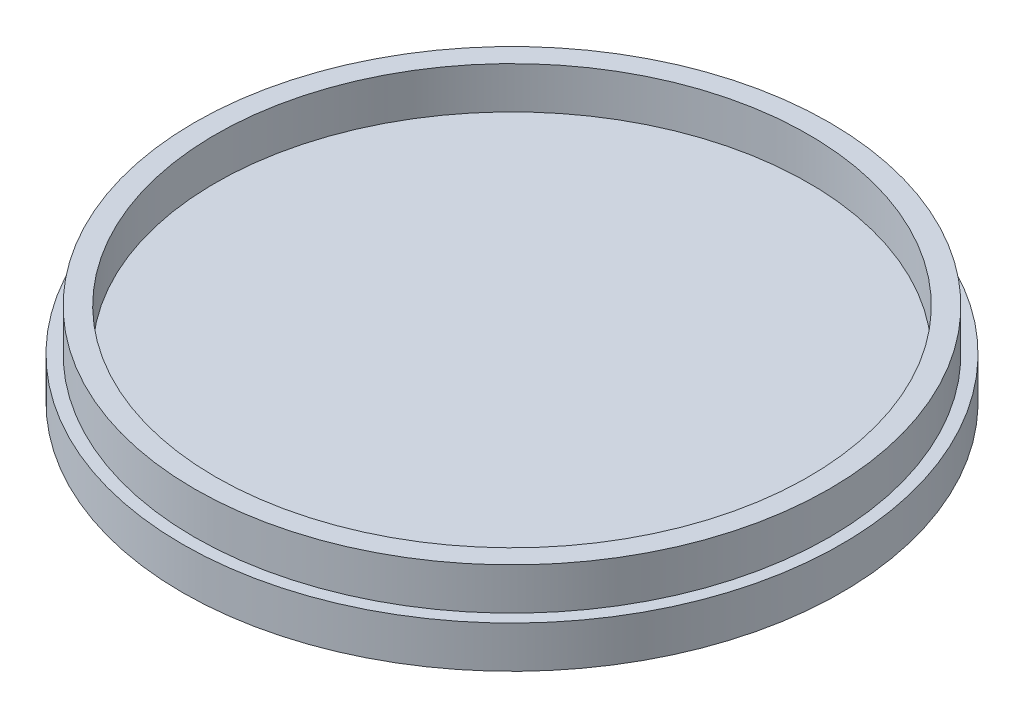
SolidWorks part; units mm, degrees
ref_plane "Front Plane" through (0, 0, 0) normal (0, 0, 1) x (1, 0, 0)
ref_plane "Top Plane" through (0, 0, 0) normal (0, 1, 0) x (1, 0, 0)
ref_plane "Right Plane" through (0, 0, 0) normal (1, 0, 0) x (0, 0, -1)
sketch "Sketch1" plane through (0, 0, 0) normal (0, 1, 0) x (1, 0, 0)
  circle A0 centre (0, 0) radius 39.4
  circle A1 centre (0, 0) radius 37.95
  circle A2 centre (0, 0) radius 35.45
  dimension "D1" = 78.8
  dimension "D2" = 75.9
  dimension "D3" = 2.5
extrude "Boss-Extrude1" add sketch "Sketch1" along normal blind 5 contours A1 A2 region at (-36.8766, 0, 0)
extrude "Boss-Extrude2" add sketch "Sketch1<4>" against normal blind 5 contours A1 A2 | A2 | A0 A1 region at (-38.2856, 0, 0) region at (-36.8766, 0, 0) region at (0, 0, 0)
sketch "Sketch1<4>" plane through (0, 0, 0) normal (0, 1, 0) x (1, 0, 0) same geometry as "Sketch1"
